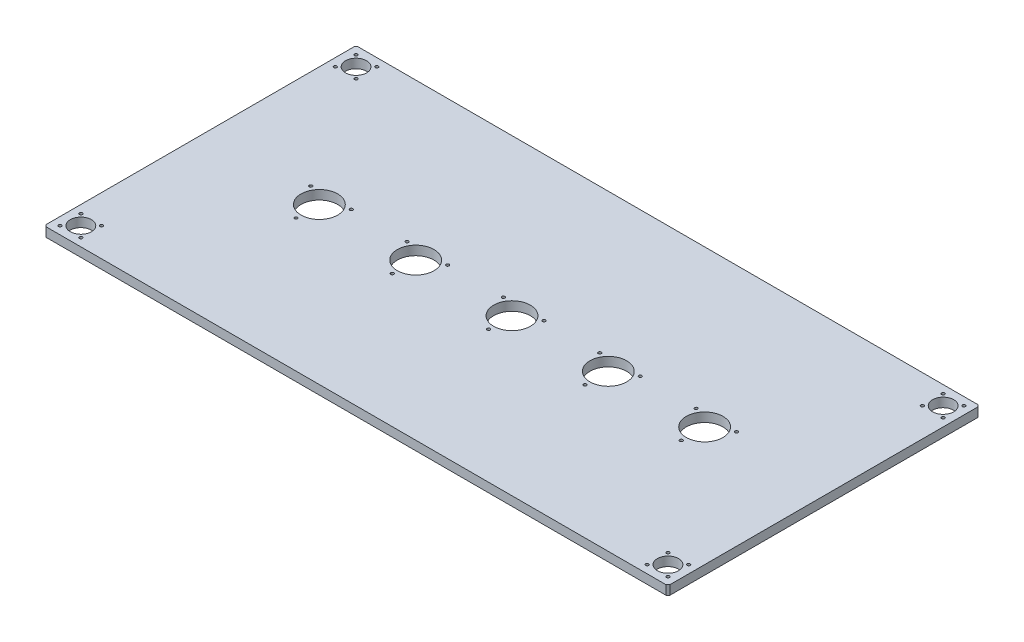
SolidWorks part; units mm, degrees
ref_plane "Front Plane" through (0, 0, 0) normal (0, 0, 1) x (1, 0, 0)
ref_plane "Top Plane" through (0, 0, 0) normal (0, 1, 0) x (1, 0, 0)
ref_plane "Right Plane" through (0, 0, 0) normal (1, 0, 0) x (0, 0, -1)
sketch "Sketch1" plane through (0, 0, 0) normal (0, 1, 0) x (1, 0, 0)
  line L0 (0, 0) -> (-340, 0) construction
  line L1 (340, 170) -> (-340, 170)
  line L2 (340, 170) -> (340, -170)
  line L3 (340, -170) -> (-340, -170)
  line L4 (-340, 170) -> (-340, -170)
  line L10 (340, 170) -> (-340, -170) construction
  line L11 (340, -170) -> (-340, 170) construction
  line L16 (0, 0) -> (0, -170) construction
  circle A4 centre (-320, -150) radius 11.5
  circle A7 centre (0, 0) radius 20
  circle A8 centre (-320, 150) radius 11.5
  circle A9 centre (320, 150) radius 11.5
  circle A10 centre (320, -150) radius 11.5
  circle A11 centre (-105, 0) radius 20
  circle A12 centre (-210, 0) radius 20
  circle A13 centre (105, 0) radius 20
  circle A14 centre (210, 0) radius 20
  point P0 (0, 0)
  dimension "D6" = 23
  dimension "D1" = 40
  dimension "D2" = 20
  dimension "D3" = 20
  dimension "D4" = 680
  dimension "D5" = 340
  dimension "D8" = 210
  dimension "D9" = 105
extrude "Boss-Extrude1" add sketch "Sketch1" along normal blind 10
chamfer "Chamfer1" distance 2 angle 45 4 edges at (340, 5, -170) (340, 5, 170) (-340, 5, 170) (-340, 5, -170)
sketch "Sketch2" plane through (0, 10, 0) normal (0, 1, 0) x (1, 0, 0)
  line L8 (-308.6863, -161.3137) -> (-331.3137, -161.3137)
  line L9 (-308.6863, -161.3137) -> (-308.6863, -138.6863)
  line L10 (-308.6863, -138.6863) -> (-331.3137, -138.6863)
  line L11 (-331.3137, -161.3137) -> (-331.3137, -138.6863)
  line L12 (-308.6863, -161.3137) -> (-331.3137, -138.6863) construction
  line L13 (-308.6863, -138.6863) -> (-331.3137, -161.3137) construction
  point P11 (-320, -150)
  dimension "D1" = 32
hole_wizard "M4x0.7 Tapped Hole1" positions "3DSketch1" profile "Sketch3" tap size "M4x0.7" standard "BSI" end condition through all
sketch3d "3DSketch1"
  point P0 (-331.3137, 10, 138.6863)
  point P3 (-308.6863, 10, 138.6863)
  point P6 (-308.6863, 10, 161.3137)
  point P9 (-331.3137, 10, 161.3137)
sketch "Sketch3" plane through (-331.3137, 10, 138.6863) normal (1, 0, 0) x (0, 0, 1)
  line L0 (0, 0) -> (0, 10)
  line L1 (0, 10) -> (1.65, 10)
  line L2 (1.65, 10) -> (1.65, 0)
  line L5 (1.65, 0) -> (0, 0)
  line L11 (0, -6.35) -> (0, 107.95) construction
  dimension "Thru Tap Drill Dia." = 3.3
  dimension "Thru Tap Drill Depth" = 10
cosmetic thread "Hole Thread4" parameters "D2"=4
cosmetic thread "Hole Thread5" parameters "D2"=4
cosmetic thread "Hole Thread6" parameters "D2"=4
cosmetic thread "Hole Thread7" parameters "D2"=4
mirror "Mirror1" about plane through (0, 0, 0) normal (0, 0, 1) of "M4x0.7 Tapped Hole1"
cosmetic thread "Hole Thread26" parameters "D2"=4
cosmetic thread "Hole Thread27" parameters "D2"=4
cosmetic thread "Hole Thread28" parameters "D2"=4
cosmetic thread "Hole Thread29" parameters "D2"=4
mirror "Mirror2" about plane through (0, 0, 0) normal (1, 0, 0) of "Mirror1"
cosmetic thread "Hole Thread30" parameters "D2"=4
cosmetic thread "Hole Thread31" parameters "D2"=4
cosmetic thread "Hole Thread32" parameters "D2"=4
cosmetic thread "Hole Thread33" parameters "D2"=4
cosmetic thread "Hole Thread34" parameters "D2"=4
cosmetic thread "Hole Thread35" parameters "D2"=4
cosmetic thread "Hole Thread36" parameters "D2"=4
cosmetic thread "Hole Thread37" parameters "D2"=4
sketch "Sketch5" plane through (0, 10, 0) normal (0, 1, 0) x (1, 0, 0)
  line L0 (0, 0) -> (0, -25.5) construction
  line L1 (0, 0) -> (22.0836, 12.75) construction
  line L2 (0, 0) -> (-22.0836, 12.75) construction
  circle A0 centre (0, 0) radius 25.5
  dimension "D1" = 51
  dimension "D2" = 120
  dimension "D3" = 120
hole_wizard "M4x0.7 Tapped Hole2" positions "3DSketch2" profile "Sketch4" tap size "M4x0.7" standard "BSI" end condition through all
sketch3d "3DSketch2"
  line L7 (0, 10, 0) -> (-22.0836, 10, -12.75) construction
  line L8 (0, 10, 0) -> (22.0836, 10, -12.75) construction
  line L9 (0, 10, 0) -> (0, 10, 25.5) construction
  circle A0 centre (0, 10, 0) radius 25.5 construction
  point P3 (-22.0836, 10, -12.75)
  point P7 (0, 35.5, 0)
  point P8 (22.0836, 10, -12.75)
  point P10 (0, 10, 25.5)
sketch "Sketch4" plane through (-22.0836, 10, -12.75) normal (1, 0, 0) x (0, 0, 1)
  line L0 (0, 0) -> (0, 10)
  line L1 (0, 10) -> (1.65, 10)
  line L2 (1.65, 10) -> (1.65, 0)
  line L5 (1.65, 0) -> (0, 0)
  line L11 (0, -6.35) -> (0, 107.95) construction
  dimension "Thru Tap Drill Dia." = 3.3
  dimension "Thru Tap Drill Depth" = 10
cosmetic thread "Hole Thread8" parameters "D2"=4
cosmetic thread "Hole Thread20" parameters "D2"=4
cosmetic thread "Hole Thread21" parameters "D2"=4
pattern_linear "LPattern1" count 3 spacing 105 along (1, 0, 0) count 3 spacing 105 along (-1, 0, 0) of "M4x0.7 Tapped Hole2"
cosmetic thread "Hole Thread38" parameters "D2"=4
cosmetic thread "Hole Thread39" parameters "D2"=4
cosmetic thread "Hole Thread40" parameters "D2"=4
cosmetic thread "Hole Thread41" parameters "D2"=4
cosmetic thread "Hole Thread42" parameters "D2"=4
cosmetic thread "Hole Thread43" parameters "D2"=4
cosmetic thread "Hole Thread44" parameters "D2"=4
cosmetic thread "Hole Thread45" parameters "D2"=4
cosmetic thread "Hole Thread46" parameters "D2"=4
cosmetic thread "Hole Thread47" parameters "D2"=4
cosmetic thread "Hole Thread48" parameters "D2"=4
cosmetic thread "Hole Thread49" parameters "D2"=4
equation "\"D9@Sketch1\"=\"D8@Sketch1\"/2"
